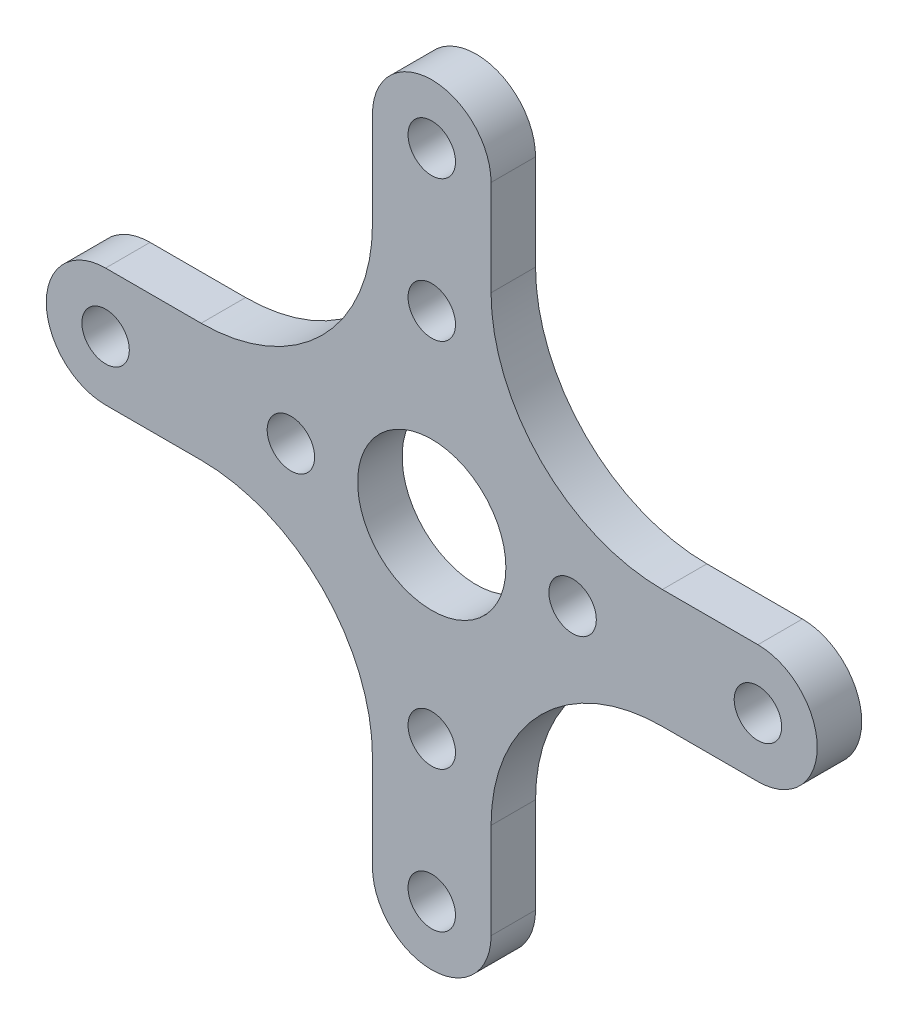
SolidWorks part; units mm, degrees
note: '?' marks a value the reader was unsure of.
ref_plane "Front Plane" through (0, 0, 0) normal (0, 0, 1) x (1, 0, 0)
ref_plane "Top Plane" through (0, 0, 0) normal (0, 1, 0) x (1, 0, 0)
ref_plane "Right Plane" through (0, 0, 0) normal (1, 0, 0) x (0, 0, -1)
sketch "Эскиз1" plane through (0, 0, 0) normal (0, 0, 1) x (1, 0, 0)
  line L0 (0, 96.3109) -> (0, -96.3109) construction
  line L1 (-81.2237, 0) -> (103.8753, 0) construction
  line L2 (-22, 4) -> (-15.5563, 4)
  line L3 (-4, 15.5563) -> (-4, 22)
  line L4 (22, 4) -> (15.5563, 4)
  line L5 (4, 15.5563) -> (4, 22)
  line L6 (22, -4) -> (15.5563, -4)
  line L7 (4, -15.5563) -> (4, -22)
  line L8 (-4, -15.5563) -> (-4, -22)
  line L9 (-22, -4) -> (-15.5563, -4)
  circle A0 centre (0, 0) radius 22 construction
  circle A1 centre (0, 22) radius 1.6
  circle A2 centre (22, 0) radius 1.6
  circle A3 centre (0, -22) radius 1.6
  circle A4 centre (-22, 0) radius 1.6
  circle A5 centre (0, 0) radius 5
  circle A6 centre (-9.5, 0) radius 1.6
  circle A7 centre (9.5, 0) radius 1.6
  circle A8 centre (0, 12.5) radius 1.6
  circle A9 centre (0, -12.5) radius 1.6
  arc A10 (-15.5563, 4) -> (-4, 15.5563) centre (-15.5563, 15.5563) ccw
  arc A11 (-4, 22) -> (4, 22) centre (0, 22) cw
  arc A12 (-22, 4) -> (-22, -4) centre (-22, 0) ccw
  arc A13 (22, 4) -> (22, -4) centre (22, 0) cw
  arc A14 (15.5563, 4) -> (4, 15.5563) centre (15.5563, 15.5563) cw
  arc A15 (15.5563, -4) -> (4, -15.5563) centre (15.5563, -15.5563) ccw
  arc A16 (-4, -22) -> (4, -22) centre (0, -22) ccw
  arc A17 (-15.5563, -4) -> (-4, -15.5563) centre (-15.5563, -15.5563) cw
  dimension "D1" = 44
  dimension "D2" = 3.2
  dimension "D4" = 3.2
  dimension "D6" = 3.2
  dimension "D9" = 10
  dimension "D3" = 19
  dimension "D5" = 9.5
  dimension "D7" = 25
  dimension "D8" = 12.5
extrude "Бобышка-Вытянуть1" add sketch "Эскиз1" along normal mid plane 3
ref_axis "Ось1" through (0, 0, 24.7187) along (0, 0, -1)?
equation "\"D5@Эскиз1\"=\"D3@Эскиз1\"/2"
equation "\"D8@Эскиз1\"=\"D7@Эскиз1\"/2"
